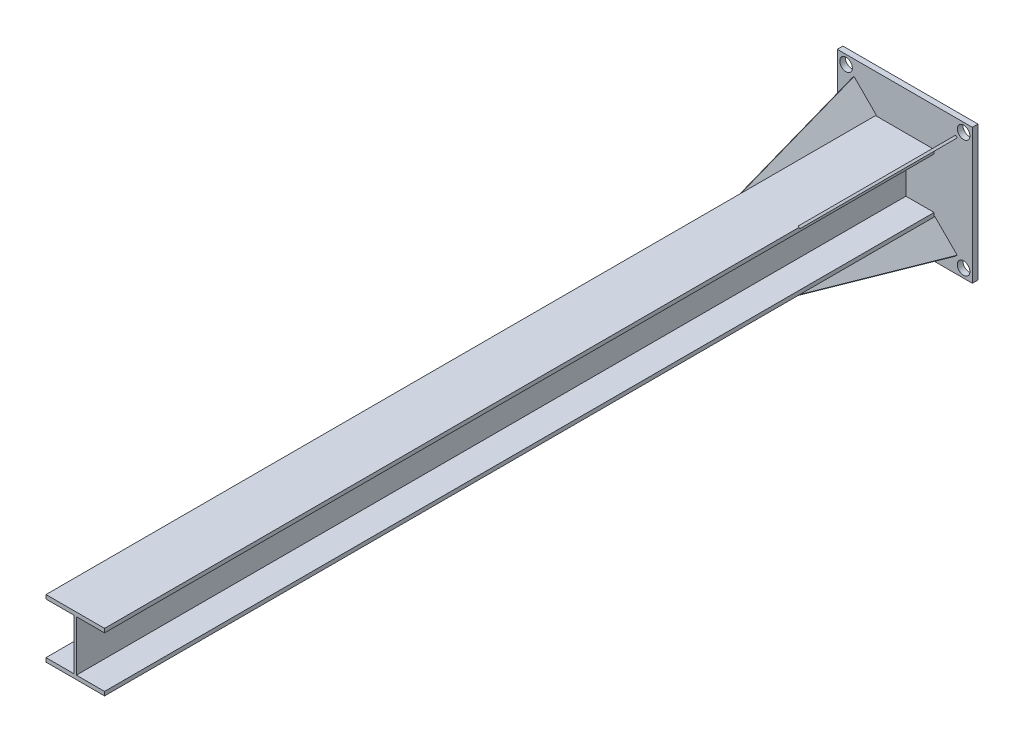
SolidWorks part; units mm, degrees
ref_plane "Front Plane" through (0, 0, 0) normal (0, 0, 1) x (1, 0, 0)
ref_plane "Top Plane" through (0, 0, 0) normal (0, 1, 0) x (1, 0, 0)
ref_plane "Right Plane" through (0, 0, 0) normal (1, 0, 0) x (0, 0, -1)
sketch "Sketch1" plane through (0, 0, 0) normal (0, 0, 1) x (1, 0, 0)
  line L0 (-125, 242.5) -> (0, 242.5)
  line L1 (-135, 17.5) -> (-260, 17.5)
  line L24 (-260, 260) -> (0, 260)
  line L25 (0, 0) -> (-260, 0)
  line L26 (-260, 260) -> (-260, 242.5)
  line L27 (-260, 242.5) -> (-135, 242.5)
  line L28 (0, 260) -> (0, 242.5)
  line L30 (-260, 0) -> (-260, 17.5)
  line L31 (0, 17.5) -> (-125, 17.5)
  line L32 (0, 0) -> (0, 17.5)
  line L34 (-135, 17.5) -> (-135, 242.5)
  line L35 (-125, 17.5) -> (-125, 242.5)
extrude "Boss-Extrude1" add sketch "Sketch1" along normal blind 3684
sketch "Sketch3" plane through (0, 0, 0) normal (0, 0, 1) x (1, 0, 0)
  line L1 (170, -170) -> (-430, -170)
  line L2 (170, -170) -> (170, 430)
  line L3 (170, 430) -> (-430, 430)
  line L4 (-430, -170) -> (-430, 430)
  line L6 (0, 260) -> (-260, 260) construction
  line L7 (-125, 17.5) -> (-125, 242.5) construction
  point P13 (-130, 260)
  point P14 (-125, 130)
  dimension "D1" = 600
  dimension "D2" = 600
  dimension "D3" = 300
  dimension "D4" = 300
extrude "Boss-Extrude2" add sketch "Sketch3" against normal blind 25 separate body
sketch "Sketch4" plane through (0, 0, 0) normal (0, 0, 1) x (1, 0, 0)
  line L0 (170, 430) -> (-430, 430) construction
  line L1 (-430, 430) -> (-430, -170) construction
  line L2 (170, -170) -> (170, 430) construction
  line L3 (-430, -170) -> (170, -170) construction
  circle A0 centre (-391, 391) radius 28
  circle A1 centre (131, 391) radius 28
  circle A2 centre (131, -131) radius 28
  circle A3 centre (-391, -131) radius 28
  dimension "D1" = 39
  dimension "D2" = 39
  dimension "D3" = 39
  dimension "D4" = 39
  dimension "D5" = 39
  dimension "D6" = 39
  dimension "D7" = 39
  dimension "D8" = 39
ref_plane "Plane1" through (0, 0, 0) normal (-0.7071, -0.7071, 0) x (0.7071, -0.7071, 0)
sketch "Sketch5" plane through (0, 0, 0) normal (-0.7071, -0.7071, 0) x (0.7071, -0.7071, 0)
  line L0 (0, 0) -> (140, 0)
  line L1 (0, 0) -> (0, 600)
  line L2 (0, 3684) -> (0, 0) construction
  line L3 (0, 600) -> (140, 0)
extrude "Boss-Extrude5" add sketch "Sketch5" along normal mid plane 10 separate body
ref_point "Point1"
ref_axis "Axis1" through (-130, 130, 3684) along (0, 0, -1)
pattern_circular "CirPattern3" count 4 over 360 about axis through (-130, 130, 3684) along (0, 0, -1) of bodies 106
sketch "Sketch6" plane through (0, 0, 0) normal (0, 0, 1) x (1, 0, 0)
  line L0 (170, -170) -> (170, 430) construction
  line L1 (170, 430) -> (-430, 430) construction
  circle A0 centre (-391, 391) radius 28
  circle A1 centre (131, 391) radius 28
  circle A2 centre (131, -131) radius 28
  circle A3 centre (-391, -131) radius 28
  dimension "D1" = 522
  dimension "D2" = 522
  dimension "D3" = 522
  dimension "D4" = 39
  dimension "D5" = 39
extrude "Cut-Extrude1" cut sketch "Sketch6" against normal through all
